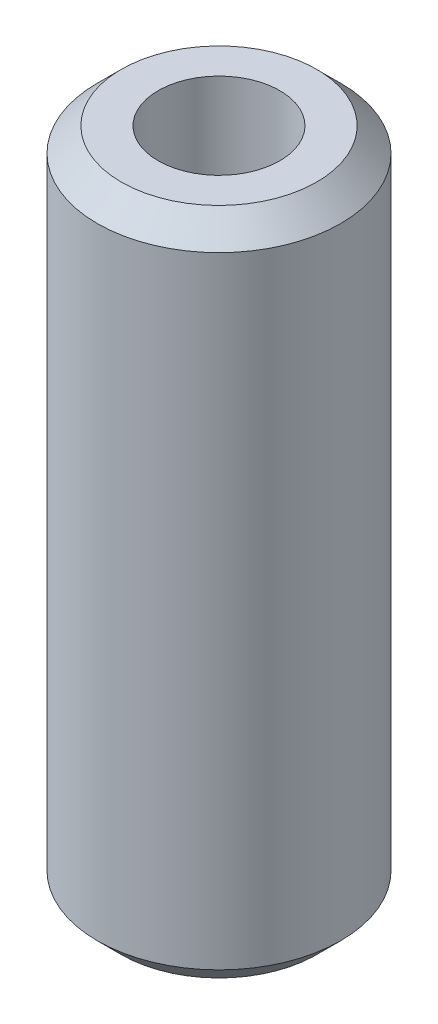
SolidWorks part; units mm, degrees
ref_plane "Front Plane" through (0, 0, 0) normal (0, 0, 1) x (1, 0, 0)
ref_plane "Top Plane" through (0, 0, 0) normal (0, 1, 0) x (1, 0, 0)
ref_plane "Right Plane" through (0, 0, 0) normal (1, 0, 0) x (0, 0, -1)
sketch "Sketch1" plane through (0, 0, 0) normal (0, 1, 0) x (1, 0, 0)
  circle A0 centre (0, 0) radius 6.35
  circle A1 centre (0, 0) radius 12.7
  dimension "D1" = 12.7
  dimension "D2" = 25.4
extrude "Boss-Extrude1" add sketch "Sketch1" along normal mid plane 69.85
chamfer "Chamfer1" distance 2.5 angle 45 2 edges at (0, -34.925, 12.7) (0, 34.925, 12.7)
scale "Scale1" scale about centroid uniform scaling yes scale factor 0.111317
